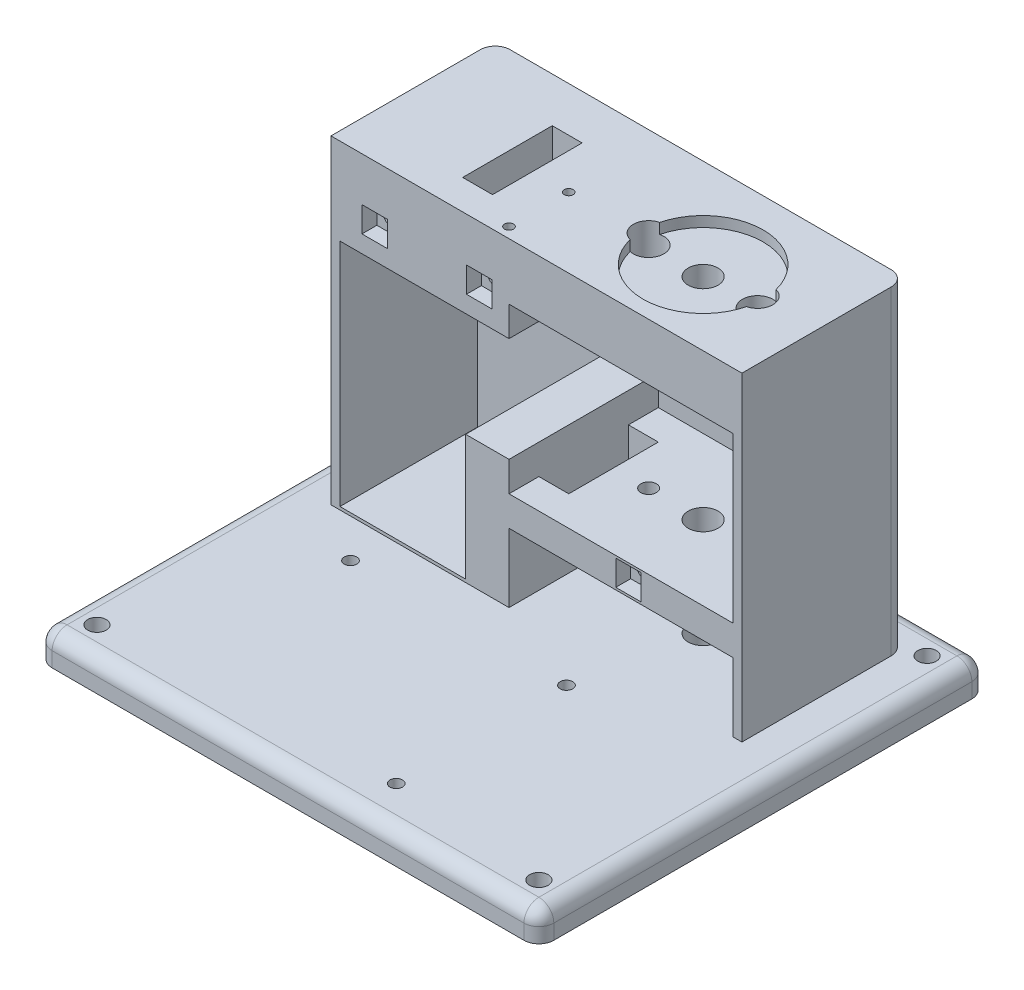
SolidWorks part; units mm, degrees
ref_plane "Front Plane" through (0, 0, 0) normal (0, 0, 1) x (1, 0, 0)
ref_plane "Top Plane" through (0, 0, 0) normal (0, 1, 0) x (1, 0, 0)
ref_plane "Right Plane" through (0, 0, 0) normal (1, 0, 0) x (0, 0, -1)
sketch "Sketch1" plane through (0, 0, 0) normal (0, 0, 1) x (1, 0, 0)
  line L0 (0, 0) -> (0, 120)
  line L11 (0, 120) -> (150, 120)
  line L12 (150, 120) -> (150, 0)
  line L13 (150, 0) -> (0, 0)
  dimension "D2" = 120
  dimension "D5" = 150
extrude "Boss-Extrude2" add sketch "Sketch1" along normal blind 70
sketch "Sketch2" plane through (0, 120, 0) normal (0, 1, 0) x (1, 0, 0)
  line L1 (150, -70) -> (150, 0) construction
  circle A0 centre (105, -35) radius 20.1
  point P8 (150, -35)
  dimension "D1" = 40.2
  dimension "D2" = 45
sketch "Sketch4" plane through (0, 0, 0) normal (0, -1, 0) x (1, 0, 0)
  line L0 (0, 70) -> (0, 0) construction
  line L1 (-9, -6) -> (159, -6)
  line L2 (-9, -6) -> (-9, 144)
  line L3 (-9, 144) -> (159, 144)
  line L4 (159, -6) -> (159, 144)
  line L5 (150, 70) -> (150, 0) construction
  line L7 (0, 0) -> (150, 0) construction
  dimension "D1" = 9
  dimension "D2" = 150
  dimension "D3" = 9
  dimension "D4" = 6
extrude "Boss-Extrude5" add sketch "Sketch4" along normal blind 3 and the other way blind 7
sketch "Sketch6" plane through (0, -3, 0) normal (0, -1, 0) x (1, 0, 0)
  line L0 (-9, 144) -> (-9, -6) construction
  line L1 (159, 144) -> (-9, 144) construction
  line L2 (159, -6) -> (159, 144) construction
  line L3 (-9, -6) -> (159, -6) construction
  circle A0 centre (1, 134) radius 3.1
  circle A1 centre (149, 134) radius 3.1
  circle A2 centre (149, 4) radius 3.1
  circle A3 centre (1, 4) radius 3.1
  dimension "D3" = 6.2
  dimension "D4" = 10
  dimension "D5" = 10
  dimension "D6" = 10
  dimension "D8" = 10
  dimension "D1" = 2
  dimension "D2" = 2
extrude "Cut-Extrude1" cut sketch "Sketch6" against normal blind 20
fillet "Fillet1" [suppressed] radius 10
fillet "Fillet2" radius 5 8 edges at (75, 7, -6) (-9, 7, 69) (159, 7, 69) (75, 7, 144) (-9, 2, -6) (159, 2, -6) (159, 2, 144) (-9, 2, 144)
extrude "Cut-Extrude2" cut sketch "Sketch2" against normal blind 9.5 contours A0
sketch "Sketch9" plane through (0, 110.5, 0) normal (0, 1, 0) x (1, 0, 0)
  circle A0 centre (105, -35) radius 5
  circle A1 centre (105, -35) radius 20.1 construction
  dimension "D1" = 10
extrude "Cut-Extrude5" cut sketch "Sketch9" against normal blind 20
sketch "Sketch15" plane through (0, 0, 70) normal (0, 0, 1) x (1, 0, 0)
  line L1 (-4, 7) -> (163.3844, 7)
  line L2 (-4, 7) -> (-4, 142.5983)
  line L3 (-4, 142.5983) -> (163.3844, 142.5983)
  line L4 (163.3844, 7) -> (163.3844, 142.5983)
extrude "Cut-Extrude12" cut sketch "Sketch15" against normal blind 10
sketch "Sketch16" plane through (0, 0, 60) normal (0, 0, 1) x (1, 0, 0)
  line L0 (0, 120) -> (150, 120) construction
  line L1 (140, 95) -> (65, 95)
  line L2 (140, 95) -> (140, 7)
  line L3 (140, 7) -> (65, 7)
  line L4 (65, 95) -> (65, 7)
  line L5 (150, 120) -> (150, 7) construction
  line L6 (0, 7) -> (150, 7) construction
  dimension "D1" = 25
  dimension "D2" = 10
  dimension "D3" = 75
extrude "Cut-Extrude13" cut sketch "Sketch16" against normal blind 50
sketch "Sketch18" plane through (0, 95, 0) normal (0, -1, 0) x (1, 0, 0)
  line L1 (65, 10) -> (140, 10)
  line L2 (65, 10) -> (65, 60)
  line L3 (65, 60) -> (140, 60)
  line L4 (140, 10) -> (140, 60)
extrude "Boss-Extrude6" add sketch "Sketch18" along normal blind 10 from offset 55
sketch "Sketch17" plane through (0, 95, 0) normal (0, -1, 0) x (1, 0, 0)
  line L0 (123.25, 35) -> (86.75, 35) construction
  circle A0 centre (123.25, 35) radius 5.1
  circle A1 centre (86.75, 35) radius 5.1
  circle A2 centre (123.25, 35) radius 2.6
  circle A3 centre (86.75, 35) radius 2.6
  point P3 (105, 35)
  point P5 (105, 35)
  dimension "D1" = 10.2
  dimension "D3" = 5.2
  dimension "D2" = 36.5
extrude "Cut-Extrude14" cut sketch "Sketch17" along normal blind 17 from surface contours A1 A3 | A3 | A2 A0 | A2 region at (118.2942, 95, 35) region at (81.7942, 95, 35) region at (123.25, 95, 35) region at (86.75, 95, 35) starting at face at (105, 120, 55.1)
extrude "Cut-Extrude15" cut sketch "Sketch17<3>" along normal up to surface (65 mm away) from surface contours A3 | A2 region at (123.25, 95, 35) region at (86.75, 95, 35) up to face at (102.5, 30, 35) starting at face at (105, 120, 35)
sketch "Sketch17<3>" plane through (0, 95, 0) normal (0, -1, 0) x (1, 0, 0) same geometry as "Sketch17"
sketch "Sketch19" plane through (65, 0, 0) normal (1, 0, 0) x (0, 0, -1)
  line L0 (-10, 95) -> (-10, 40) construction
  line L1 (-10, 85) -> (-60, 85)
  line L2 (-10, 85) -> (-10, 50)
  line L3 (-10, 50) -> (-60, 50)
  line L4 (-60, 85) -> (-60, 50)
  line L5 (-60, 95) -> (-60, 40) construction
  line L6 (-10, 95) -> (-60, 95) construction
  line L7 (-60, 40) -> (-10, 40) construction
  dimension "D1" = 10
  dimension "D2" = 10
extrude "Cut-Extrude19" cut sketch "Sketch19" against normal blind 56.62
sketch "Sketch20" plane through (0, 0, 60) normal (0, 0, 1) x (1, 0, 0)
  line L0 (29.43, 83) -> (29.43, 8) construction
  line L1 (8.38, 8) -> (50.48, 8)
  line L2 (8.38, 8) -> (8.38, 58)
  line L3 (8.38, 58) -> (25.43, 58)
  line L4 (50.48, 8) -> (50.48, 58)
  line L7 (105, 95) -> (105, 59.9679) construction
  line L8 (25.43, 58) -> (25.43, 83)
  line L9 (25.43, 83) -> (33.43, 83)
  line L10 (33.43, 83) -> (33.43, 58)
  line L11 (33.43, 58) -> (50.48, 58)
  line L12 (8.38, 85) -> (65, 85) construction
  point P11 (29.43, 83)
  dimension "D1" = 42.1
  dimension "D2" = 75.57
  dimension "D3" = 50
  dimension "D4" = 25
  dimension "D5" = 8
  dimension "D6" = 2
extrude "Cut-Extrude20" cut sketch "Sketch20" against normal blind 46
sketch "Sketch21" plane through (0, 0, 0) normal (0, 0, -1) x (-1, 0, 0)
  line L0 (0, 120) -> (-150, 120) construction
  line L1 (0, 7) -> (0, 120) construction
  line L2 (-78.7578, 35) -> (-118.062, 35) construction
  line L3 (-140, 40) -> (-65, 40) construction
  line L4 (-140, 30) -> (-65, 30) construction
  circle A0 centre (-20, 95) radius 2
  circle A2 centre (-105, 35) radius 2
  circle A3 centre (-55, 95) radius 2
  dimension "D1" = 4
  dimension "D2" = 25
  dimension "D3" = 20
  dimension "D4" = 35
extrude "Cut-Extrude21" cut sketch "Sketch21" along normal blind 25 from surface starting at face at (65.772, 55.6, 60)
extrude "Cut-Extrude24" cut sketch "Sketch9<4>" against normal blind 150
sketch "Sketch9<4>" plane through (0, 110.5, 0) normal (0, 1, 0) x (1, 0, 0) same geometry as "Sketch9"
sketch "Sketch22" plane through (0, 40, 0) normal (0, 1, 0) x (1, 0, 0)
  line L0 (63.8113, -35) -> (76.8208, -35) construction
  line L1 (65, -20) -> (75, -20)
  line L2 (65, -20) -> (65, -50)
  line L3 (65, -50) -> (75, -50)
  line L4 (75, -20) -> (75, -50)
  line L5 (65, -20) -> (75, -50) construction
  line L6 (65, -50) -> (75, -20) construction
  line L7 (140, -60) -> (65, -60) construction
  line L8 (65, -10) -> (140, -10) construction
  line L9 (65, -60) -> (65, -10) construction
  point P0 (70, -35)
  dimension "D1" = 30
  dimension "D2" = 10
extrude "Cut-Extrude25" cut sketch "Sketch22" along normal blind 29 from surface starting at face at (100, 30, 35)
sketch "Sketch23" plane through (0, 7, 0) normal (0, 1, 0) x (1, 0, 0)
  line L5 (-4, 1) -> (-4, -139) construction
  line L6 (16.4788, -65.9044) -> (106.4788, -65.9044)
  line L10 (18.4788, -134.9044) -> (103.4788, -134.9044)
  line L11 (0, -6.9343) -> (0, -60) construction
  line L12 (0, -60) -> (65, -60) construction
  line L13 (18.4788, -134.9044) -> (18.4788, -67.9044)
  line L14 (18.4788, -67.9044) -> (103.4788, -67.9044)
  line L15 (103.4788, -134.9044) -> (103.4788, -67.9044)
  line L16 (18.4788, -134.9044) -> (103.4788, -67.9044) construction
  line L17 (18.4788, -67.9044) -> (103.4788, -134.9044) construction
  line L18 (106.4788, -136.9044) -> (106.4788, -65.9044)
  line L19 (16.4788, -136.9044) -> (106.4788, -136.9044)
  line L20 (16.4788, -136.9044) -> (16.4788, -65.9044)
  circle A0 centre (24.8221, -72.9044) radius 2.1
  circle A1 centre (97.1355, -72.9044) radius 2.1
  circle A2 centre (97.1355, -129.9044) radius 2.1
  circle A3 centre (24.8221, -72.9044) radius 4
  circle A4 centre (97.1355, -72.9044) radius 4
  circle A5 centre (97.1355, -129.9044) radius 4
  point P0 (59, -106.5)
  point P5 (60.9788, -101.4044)
  dimension "D1" = 46.5
  dimension "D5" = 4.2
  dimension "D7" = 8
  dimension "D2" = 63
  dimension "D3" = 85
  dimension "D4" = 67
  dimension "D6" = 5
  dimension "D8" = 71
  dimension "D9" = 90
extrude "Cut-Extrude26" cut sketch "Sketch23" against normal through all contours A0 | A1 | A2 region at (24.8221, 7, 72.9044) region at (97.1355, 7, 72.9044) region at (97.1355, 7, 129.9044)
extrude "Cut-Extrude27" cut sketch "Sketch23<3>" along normal blind 5 from surface contours A3 | A4 | A5 starting at face at (22.7221, -3, 72.9044)
sketch "Sketch23<3>" plane through (0, 7, 0) normal (0, 1, 0) x (1, 0, 0) same geometry as "Sketch23"
sketch "Sketch24" plane through (0, 120, 0) normal (0, 1, 0) x (1, 0, 0)
  line L0 (61.5, -56.5) -> (61.5, -36.5) construction
  circle A0 centre (61.5, -36.5) radius 1.5
  circle A1 centre (61.5, -56.5) radius 1.5
  dimension "D1" = 3
extrude "Cut-Extrude28" cut sketch "Sketch24" against normal blind 30
sketch "Sketch25" plane through (0, 120, 0) normal (0, 1, 0) x (1, 0, 0)
  line L0 (49.48, -20) -> (49.48, -50)
  line L1 (49.48, -50) -> (39.48, -50)
  line L2 (39.48, -50) -> (39.48, -20)
  line L3 (39.48, -20) -> (49.48, -20)
  line L4 (65, -20) -> (65, -50) construction
  line L5 (65, -20) -> (75, -20) construction
  line L6 (65, -50) -> (75, -50) construction
  dimension "D1" = 1
extrude "Cut-Extrude29" cut sketch "Sketch25" against normal blind 40
sketch "Sketch27" plane through (0, 0, 60) normal (0, 0, 1) x (1, 0, 0)
  line L0 (124.4812, 110.5) -> (85.5188, 110.5) construction
  line L1 (143, 114) -> (5.38, 114)
  line L2 (160.4669, 109) -> (160.4669, 126.652)
  line L3 (160.4669, 126.652) -> (-15.0397, 126.652)
  line L4 (-15.0397, 109) -> (-15.0397, 126.652)
  line L5 (5.38, 114) -> (5.38, 7)
  line L6 (5.38, 7) -> (-15.0397, 7)
  line L7 (-15.0397, 7) -> (-15.0397, 109)
  line L8 (160.4669, 109) -> (160.4669, 7)
  line L9 (160.4669, 7) -> (143, 7)
  line L10 (-4, 7) -> (154, 7) construction
  line L11 (143, 7) -> (143, 114)
  line L12 (8.38, 85) -> (8.38, 8) construction
  line L13 (140, 40) -> (140, 95) construction
  dimension "D1" = 3.5
  dimension "D2" = 3
  dimension "D3" = 3
extrude "Cut-Extrude30" cut sketch "Sketch27" against normal blind 196
sketch "Sketch29" plane through (5.38, 0, 0) normal (-1, 0, 0) x (0, 0, 1)
  line L0 (-8.9375, 135.3916) -> (5, 135.3916)
  line L1 (5, 135.3916) -> (5, 7)
  line L2 (-1, 7) -> (139, 7) construction
  line L3 (5, 7) -> (-13.4834, 7)
  line L4 (-13.4834, 7) -> (-8.9375, 135.3916)
  line L5 (10, 50) -> (10, 85) construction
  dimension "D1" = 5
extrude "Cut-Extrude32" cut sketch "Sketch29" against normal blind 196
sketch "Sketch30" plane through (0, 50, 0) normal (0, 1, 0) x (1, 0, 0)
  line L0 (50.48, -14) -> (50.48, -60) construction
  line L1 (53.48, -17) -> (62, -17)
  line L2 (53.48, -17) -> (53.48, -57)
  line L3 (53.48, -57) -> (62, -57)
  line L4 (62, -17) -> (62, -57)
  line L5 (65, -60) -> (65, -10) construction
  line L6 (50.48, -60) -> (65, -60) construction
  line L7 (8.38, -14) -> (50.48, -14) construction
  dimension "D1" = 3
  dimension "D2" = 3
  dimension "D3" = 3
  dimension "D4" = 3
extrude "Cut-Extrude33" cut sketch "Sketch30" against normal offset from surface (37 mm away) 3 from offset 3 up to face at (145.9, 7, 4) offset against normal yes
fillet "Fillet3" radius 5 2 edges at (143, 60.5, 5) (5.38, 60.5, 5)
sketch "Sketch31" plane through (0, 0, 60) normal (0, 0, 1) x (1, 0, 0)
  line L1 (37.9028, 110.4016) -> (25.5493, 110.4016)
  line L2 (37.9028, 110.4016) -> (37.9028, 87.424)
  line L3 (37.9028, 87.424) -> (25.5493, 87.424)
  line L4 (25.5493, 100.1553) -> (25.5493, 87.424)
  line L5 (25.5493, 110.4016) -> (13.7354, 110.4016)
  line L7 (25.5493, 100.1553) -> (13.7354, 100.1553)
  line L8 (13.7354, 110.4016) -> (13.7354, 100.1553)
  line L13 (52.8106, 111.0095) -> (58.3615, 111.0095)
  line L14 (52.8106, 111.0095) -> (52.8106, 100.8745)
  line L15 (52.8106, 100.8745) -> (58.3615, 100.8745)
  line L16 (58.3615, 111.0095) -> (58.3615, 100.8745)
  line L17 (65.7309, 111.0247) -> (80.4236, 111.0247)
  line L18 (65.7309, 111.0247) -> (65.7309, 98.0844)
  line L19 (65.7309, 98.0844) -> (80.4236, 98.0844)
  line L20 (80.4236, 111.0247) -> (80.4236, 98.0844)
extrude "Cut-Extrude34" cut sketch "Sketch31" against normal offset from surface (49 mm away) 3 from offset 3 up to face at (74.19, 60.5, 5) offset against normal yes
sketch "Sketch32" plane through (0, 0, 60) normal (0, 0, 1) x (1, 0, 0)
  line L1 (15.75, 90.75) -> (24.25, 90.75)
  line L2 (15.75, 90.75) -> (15.75, 99.25)
  line L3 (15.75, 99.25) -> (24.25, 99.25)
  line L4 (24.25, 90.75) -> (24.25, 99.25)
  line L5 (15.75, 90.75) -> (24.25, 99.25) construction
  line L6 (15.75, 99.25) -> (24.25, 90.75) construction
  line L7 (59.25, 99.25) -> (50.75, 99.25)
  line L8 (59.25, 99.25) -> (59.25, 90.75)
  line L9 (59.25, 90.75) -> (50.75, 90.75)
  line L10 (50.75, 99.25) -> (50.75, 90.75)
  line L11 (59.25, 99.25) -> (50.75, 90.75) construction
  line L12 (59.25, 90.75) -> (50.75, 99.25) construction
  line L13 (109.25, 39.25) -> (100.75, 39.25)
  line L14 (109.25, 39.25) -> (109.25, 30.75)
  line L15 (109.25, 30.75) -> (100.75, 30.75)
  line L16 (100.75, 39.25) -> (100.75, 30.75)
  line L17 (109.25, 39.25) -> (100.75, 30.75) construction
  line L18 (109.25, 30.75) -> (100.75, 39.25) construction
  point P0 (20, 95)
  point P6 (55, 95)
  point P12 (105, 35)
  dimension "9" = 8.5
extrude "Cut-Extrude37" cut sketch "Sketch32" against normal blind 5
